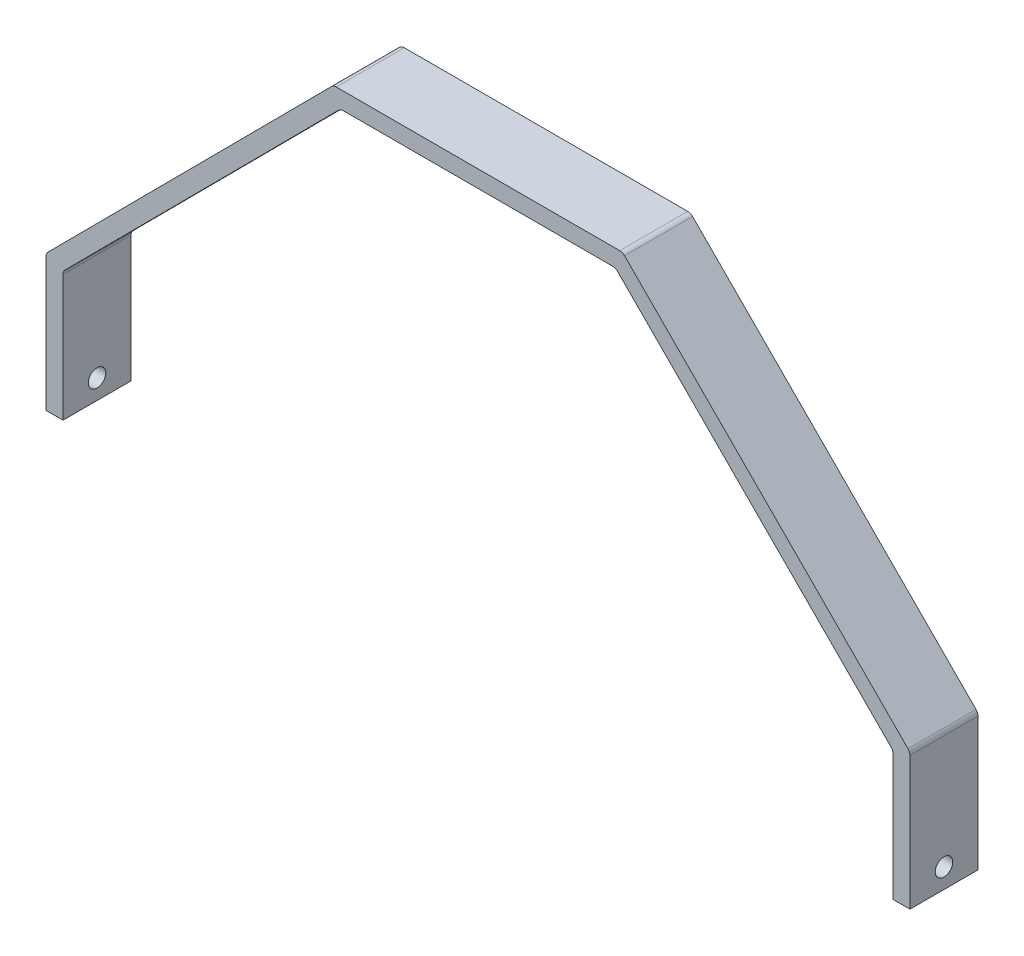
SolidWorks part; units mm, degrees
material "Thornel VCB-20 Carbon Cloth"
ref_plane "Front Plane" through (0, 0, 0) normal (0, 0, 1) x (1, 0, 0)
ref_plane "Top Plane" through (0, 0, 0) normal (0, 1, 0) x (1, 0, 0)
ref_plane "Right Plane" through (0, 0, 0) normal (1, 0, 0) x (0, 0, -1)
sketch "Sketch1" plane through (0, 0, 0) normal (0, 0, 1) x (1, 0, 0)
  line L0 (42.5, 0) -> (-42.5, 0)
  line L1 (42.5, 0) -> (127, -85)
  line L2 (127, -85) -> (127, -125)
  line L3 (-42.5, 0) -> (-127, -85)
  line L4 (-127, -85) -> (-127, -125)
  line L5 (122, -87.0624) -> (122, -125)
  line L6 (40.4203, -5) -> (122, -87.0624)
  line L7 (40.4203, -5) -> (-40.4203, -5)
  line L8 (-40.4203, -5) -> (-122, -87.0624)
  line L9 (-122, -87.0624) -> (-122, -125)
  line L10 (-127, -125) -> (-122, -125)
  line L11 (122, -125) -> (127, -125)
  point P4 (0, 0)
  dimension "D1" = 85
  dimension "D2" = 254
  dimension "D3" = 125
  dimension "D4" = 127
  dimension "D5" = 40
  dimension "D6" = 5
extrude "Boss-Extrude1" add sketch "Sketch1" along normal blind 20
fillet "Fillet1" radius 2 8 edges at (122, -87.0624, 10) (40.4203, -5, 10) (-40.4203, -5, 10) (-122, -87.0624, 10) (-127, -85, 10) (127, -85, 10) (-42.5, 0, 10) (42.5, 0, 10)
sketch "Sketch2" plane through (-127, 0, 0) normal (-1, 0, 0) x (0, 0, 1)
  line L0 (0, -125) -> (10, -125) construction
  line L1 (20, -125) -> (0, -125) construction
  line L2 (10, -125) -> (10, -85.825) construction
  line L3 (20, -85.825) -> (0, -85.825) construction
  line L4 (0, -105.4125) -> (20, -105.4125) construction
  line L5 (0, -85.825) -> (0, -125) construction
  line L6 (20, -85.825) -> (20, -125) construction
  circle A0 centre (10, -105.4125) radius 2.5
  circle A1 centre (10, -119.231) radius 2.5748
  dimension "D1" = 5
extrude "Cut-Extrude1" cut sketch "Sketch2" against normal through all contours A1
